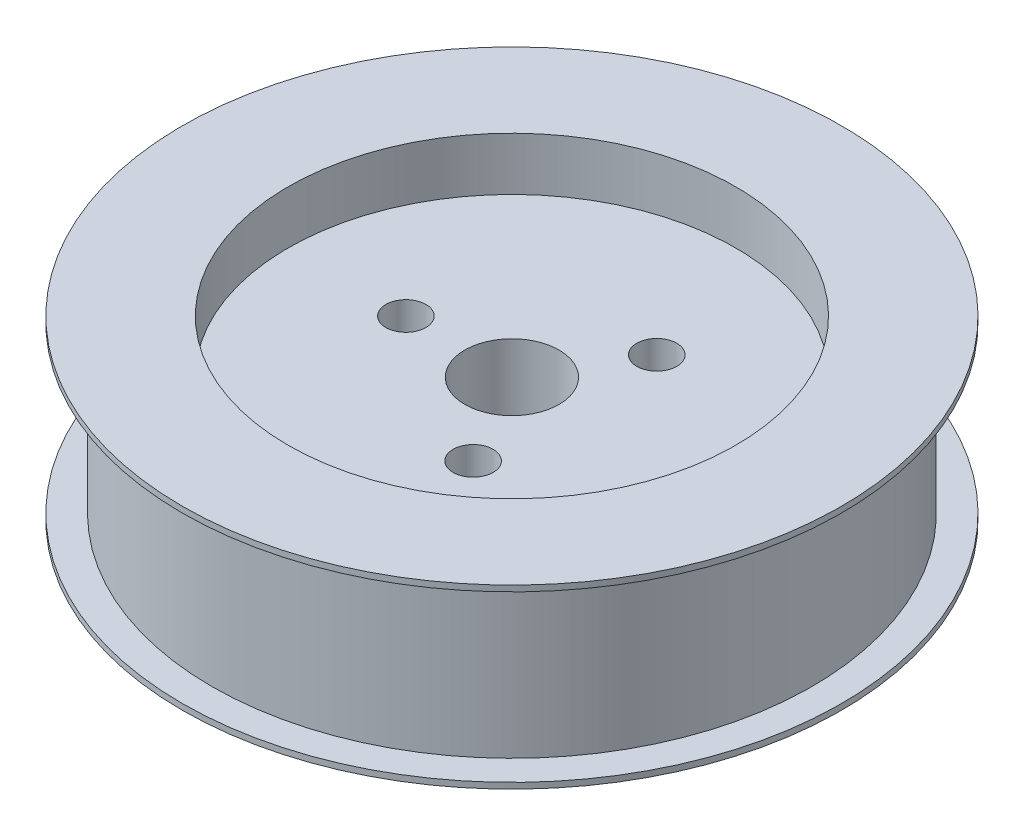
SolidWorks part; units mm, degrees
ref_plane "Alzado" through (0, 0, 0) normal (1, 0, 0) x (0, 1, 0)
ref_plane "Planta" through (0, 0, 0) normal (0, 0, 1) x (0, 1, 0)
ref_plane "Vista lateral" through (0, 0, 0) normal (0, 1, 0) x (-1, 0, 0)
sketch "Croquis1" plane through (0, 0, 0) normal (0, 1, 0) x (-1, 0, 0)
  circle A0 centre (0, 0) radius 25.47
  dimension "D1" = 50.94
extrude "Saliente-Extruir1" add sketch "Croquis1" along normal mid plane 15
sketch "Croquis2" plane through (0, 7.5, 0) normal (0, 1, 0) x (-1, 0, 0)
  circle A3 centre (0, 0) radius 27.97
  dimension "D1" = 55.94
extrude "Saliente-Extruir2" add sketch "Croquis2" against normal blind 0.5
extrude "Saliente-Extruir3" add sketch "Croquis2<2>" along normal blind 0.5 from surface starting at face at (0, -7.5, 25.47)
sketch "Croquis2<2>" plane through (0, 7.5, 0) normal (0, 1, 0) x (-1, 0, 0) same geometry as "Croquis2"
sketch "Croquis3" plane through (0, -7.5, 0) normal (0, 1, 0) x (-1, 0, 0)
  circle A0 centre (0, 0) radius 19
  dimension "D1" = 38
extrude "Saliente-Extruir4" add sketch "Croquis3" along normal blind 21
sketch "Croquis4" plane through (0, -7, 0) normal (0, 1, 0) x (-1, 0, 0)
  circle A0 centre (0, 0) radius 4
  dimension "D1" = 8
extrude "Cortar-Extruir1" cut sketch "Croquis4" against normal through all both and the other way through all
sketch "Croquis5" plane through (0, 13.5, 0) normal (0, 1, 0) x (-1, 0, 0)
  circle A0 centre (0, 0) radius 19
  circle A1 centre (0, 0) radius 19 construction
extrude "Cortar-Extruir2" cut sketch "Croquis5" against normal offset from surface (10.5 mm away) 3 up to plane "Vista lateral"
mirror "Simetría1" about plane through (0, 0, 0) normal (0, 1, 0) of "Cortar-Extruir2"
sketch "Croquis6" plane through (0, 7.5, 0) normal (0, 1, 0) x (-1, 0, 0)
  circle A0 centre (0, 0) radius 9 construction
  point P3 (9, 0)
  point P4 (-4.5, -7.7942)
  point P7 (-4.5, 7.7942)
  point P8 (0, 0)
  dimension "D1" = 18
  dimension "D2" = 3
hole_wizard "Taladro de margen para M31" positions "Croquis6" profile "Croquis7" hole size "M3" standard "Ansi Metric" end condition through all
sketch "Croquis7" plane through (0, 7.5, 0) normal (1, 0, 0) x (0, 0, 1)
  line L0 (0, 0) -> (0, 15)
  line L1 (0, 15) -> (1.7, 15)
  line L2 (1.7, 15) -> (1.7, 0)
  line L5 (1.7, 0) -> (0, 0)
  line L11 (0, -6.35) -> (0, 107.95) construction
  dimension "Diámetro de taladro hasta el siguiente" = 3.4
  dimension "Profundidad de taladro hasta el siguiente" = 15
equation "\"Dp\"= 50.94"
equation "\"D1@Croquis1\"=\"Dp\""
equation "\"Dm\"= 38"
equation "\"De\"= \"Dp\" + 5"
equation "\"F\"= 15"
equation "\"L\"= 21"
equation "\"D1@Croquis2\"=\"De\""
equation "\"D1@Saliente-Extruir1\"=\"F\""
equation "\"D1@Saliente-Extruir4\"=\"L\""
equation "\"deje\"=8"
equation "\"D1@Croquis4\"=\"deje\""
equation "\"D1@Croquis3\"=\"Dm\""
